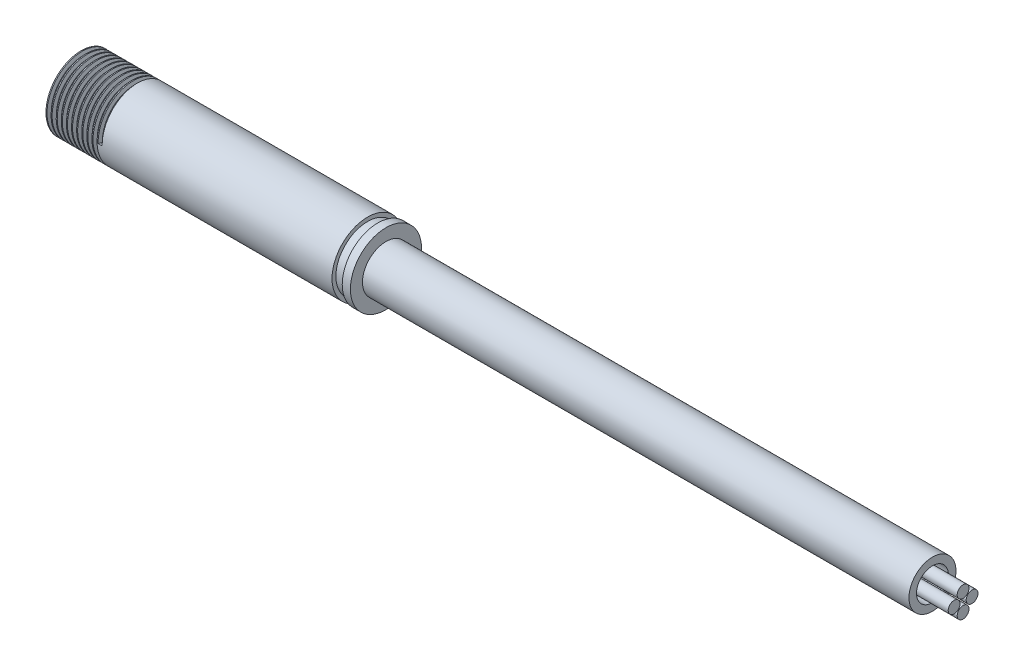
SolidWorks part; units mm, degrees
ref_plane "Front Plane" through (0, 0, 0) normal (0, 0, 1) x (1, 0, 0)
ref_plane "Top Plane" through (0, 0, 0) normal (0, 1, 0) x (1, 0, 0)
ref_plane "Right Plane" through (0, 0, 0) normal (1, 0, 0) x (0, 0, -1)
sketch "Sketch1" plane through (0, 0, 0) normal (1, 0, 0) x (0, 0, -1)
  circle A0 centre (0, 0) radius 3.48
  dimension "D1" = 6.96
extrude "Boss-Extrude1" add sketch "Sketch1" along normal blind 30
sketch "Sketch2" plane through (0, 0, 0) normal (-1, 0, 0) x (0, 0, 1)
  circle A1 centre (0, 0) radius 2
  circle A2 centre (0, 0) radius 2.98
  circle A3 centre (0, 0) radius 2.98
  dimension "D2" = 4
  dimension "D1" = 0.5
extrude "Cut-Extrude1" cut sketch "Sketch2" against normal blind 2
sketch "Sketch3" plane through (0, 0, 0) normal (-1, 0, 0) x (0, 0, 1)
  circle A0 centre (0, 0) radius 0.7487
  dimension "D1" = 1.4975
extrude "Cut-Extrude2" cut sketch "Sketch3" against normal blind 1
sketch "Sketch4" plane through (2, 0, 0) normal (-1, 0, 0) x (0, 0, 1)
  line L0 (0, 0) -> (0, 2.0765) construction
  line L2 (-0.7301, 2.844) -> (0.7301, 2.844)
  line L3 (-0.7301, 2.844) -> (-0.7301, 2.0765)
  line L4 (-0.7301, 2.0765) -> (0.7301, 2.0765)
  line L5 (0.7301, 2.844) -> (0.7301, 2.0765)
  line L6 (-0.7301, 2.844) -> (0.7301, 2.0765) construction
  line L7 (-0.7301, 2.0765) -> (0.7301, 2.844) construction
  point P3 (0, 2.4603)
extrude "Boss-Extrude2" add sketch "Sketch4" along normal blind 1.5
pattern_circular "CirPattern1" count 6 over 360 about axis through (2, 0, 0) along (-1, 0, 0) of "Boss-Extrude2"
sketch "Sketch5" plane through (0, 0, 0) normal (-1, 0, 0) x (0, 0, 1)
  circle A0 centre (0, 0) radius 3.48 construction
  circle A1 centre (0, 0) radius 3.48
curve "Helix/Spiral1" pitch 0.5 height 5.5 radius 3.48 centre (0, 0, 0) axis (1, 0, 0) start towards (0, 0, 1)
sketch "Sketch6" plane through (0, 0, 0) normal (0, 1, 0) x (1, 0, 0)
  line L0 (-0.0813, -3.18) -> (0.0813, -3.18)
  line L2 (0.0813, -3.18) -> (0.2, -3.48)
  line L3 (0.2, -3.48) -> (-0.2, -3.48)
  line L4 (-0.2, -3.48) -> (-0.0813, -3.18)
  line L6 (0, -3.48) -> (0, -3.18) construction
  dimension "D1" = 0.4
  dimension "D2" = 0.3
sweep "Cut-Sweep2" cut profiles "Sketch6" path "Helix/Spiral1" align with end faces yes
sketch "Sketch7" plane through (0, 0, 0) normal (-1, 0, 0) x (0, 0, 1)
  circle A0 centre (0, 0) radius 4.6212
  circle A1 centre (0, 0) radius 3.1
  dimension "D1" = 6.2
extrude "Cut-Extrude3" cut sketch "Sketch7" against normal blind 1 from offset 28.2 offset against normal yes
sketch "Sketch8" plane through (30, 0, 0) normal (1, 0, 0) x (0, 0, -1)
  circle A0 centre (0, 0) radius 2.3
  dimension "D1" = 4.6
extrude "Boss-Extrude3" add sketch "Sketch8" along normal blind 53.5
sketch "Sketch9" plane through (83.5, 0, 0) normal (1, 0, 0) x (0, 0, -1)
  circle A0 centre (0, 0) radius 1.5618
extrude "Cut-Extrude4" cut sketch "Sketch9" against normal blind 5
sketch "Sketch10" plane through (78.5, 0, 0) normal (1, 0, 0) x (0, 0, -1)
  line L0 (0, 0) -> (0, 0.8798) construction
  circle A0 centre (0, 0.8798) radius 0.5786
  circle A1 centre (0.8798, 0) radius 0.5786
  circle A2 centre (0, -0.8798) radius 0.5786
  circle A3 centre (-0.8798, 0) radius 0.5786
  point P14 (0, 0)
  dimension "D1" = 4
extrude "Boss-Extrude4" add sketch "Sketch10" along normal blind 8
